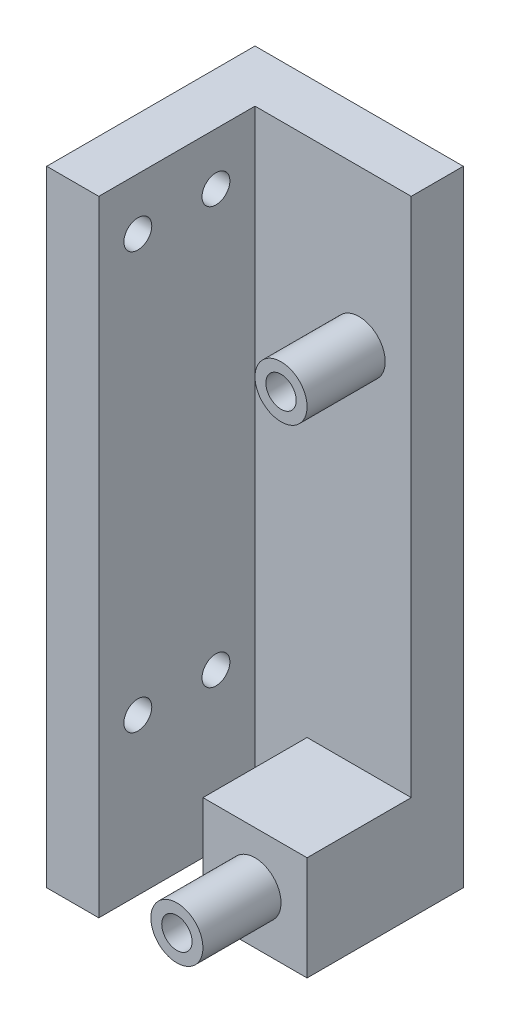
SolidWorks part; units mm, degrees
ref_plane "Front Plane" through (0, 0, 0) normal (0, 0, 1) x (1, 0, 0)
ref_plane "Top Plane" through (0, 0, 0) normal (0, 1, 0) x (1, 0, 0)
ref_plane "Right Plane" through (0, 0, 0) normal (1, 0, 0) x (0, 0, -1)
sketch "Sketch1" plane through (0, 0, 0) normal (0, 0, 1) x (1, 0, 0)
  line L1 (0, 0) -> (25.4, 0)
  line L2 (0, 0) -> (0, 76.2)
  line L3 (0, 76.2) -> (25.4, 76.2)
  line L4 (25.4, 0) -> (25.4, 76.2)
  dimension "D1" = 76.2
  dimension "D2" = 25.4
extrude "Boss-Extrude1" add sketch "Sketch1" against normal blind 25.4
sketch "Sketch10" plane through (25.4, 0, 0) normal (1, 0, 0) x (0, 0, -1)
  line L0 (25.4, 76.2) -> (0, 76.2) construction
  line L1 (19.05, 76.2) -> (0, 76.2)
  line L2 (19.05, 76.2) -> (19.05, 0)
  line L3 (19.05, 0) -> (0, 0)
  line L4 (0, 76.2) -> (0, 0)
  line L5 (25.4, 0) -> (0, 0) construction
  line L6 (25.4, 0) -> (25.4, 76.2) construction
  line L8 (0, 0) -> (0, 76.2) construction
  dimension "D1" = 6.35
extrude "Cut-Extrude5" cut sketch "Sketch10" against normal offset from surface (19.05 mm away) 6.35 up to face at (0, 38.1, -12.7)
sketch "Sketch12" plane through (0, 0, -25.4) normal (0, 0, -1) x (-1, 0, 0)
  line L0 (-25.4, 76.2) -> (0, 76.2) construction
  line L1 (-25.4, 0) -> (-25.4, 76.2) construction
  circle A1 centre (-19.05, 57.15) radius 3.175
  circle A2 centre (-19.05, 57.15) radius 1.85
  dimension "D2" = 6.35
  dimension "D4" = 3.7
  dimension "D1" = 19.05
  dimension "D3" = 6.35
extrude "Boss-Extrude2" add sketch "Sketch12" against normal blind 9.525 from surface starting at face at (15.875, 38.1, -19.05)
sketch "Sketch13" plane through (0, 0, -25.4) normal (0, 0, -1) x (-1, 0, 0)
  line L1 (-25.4, 0) -> (-12.7, 0)
  line L3 (-25.4, 12.7) -> (-12.7, 12.7)
  line L4 (-12.7, 0) -> (-12.7, 12.7)
  line L5 (-25.4, 12.7) -> (-25.4, 0)
  dimension "D2" = 12.7
  dimension "D3" = 12.7
extrude "Boss-Extrude3" add sketch "Sketch13" against normal blind 12.7 from surface starting at face at (19.05, 60.325, -19.05)
sketch "Sketch14" plane through (0, 0, -6.35) normal (0, 0, 1) x (1, 0, 0)
  line L1 (25.4, 0) -> (12.7, 0) construction
  line L2 (25.4, 12.7) -> (25.4, 76.2) construction
  circle A0 centre (19.05, 6.35) radius 1.85
  circle A1 centre (19.05, 6.35) radius 3.175
  circle A3 centre (19.05, 57.15) radius 1.85 construction
  circle A4 centre (19.05, 57.15) radius 3.175 construction
  dimension "D1" = 6.35
  dimension "D2" = 6.35
extrude "Boss-Extrude4" add sketch "Sketch14" along normal blind 9.525
sketch "Sketch15" plane through (6.35, 0, 0) normal (1, 0, 0) x (0, 0, -1)
  line L1 (19.05, 76.2) -> (0, 76.2) construction
  line L2 (0, 76.2) -> (0, 0) construction
  line L3 (19.05, 12.7) -> (19.05, 76.2) construction
  line L4 (0, 0) -> (19.05, 0) construction
  circle A0 centre (4.7625, 69.85) radius 1.7
  circle A1 centre (14.2875, 69.85) radius 1.7
  circle A2 centre (4.7625, 19.05) radius 1.7
  circle A3 centre (14.2875, 19.05) radius 1.7
  point P8 (0, 0)
  dimension "D2" = 6.35
  dimension "D1" = 3.4
  dimension "D3" = 4.7625
  dimension "D4" = 4.7625
  dimension "D5" = 19.05
extrude "Cut-Extrude6" cut sketch "Sketch15" against normal through all
equation "\"D4@Sketch12\"= 3.7mm"
equation "\"D1@Boss-Extrude1\"=(0.375+15.7mm)+0.25+0.25"
equation "\"tightTol\"= 0.005in"
equation "\"normTol\"= 0.01in"
equation "\"looseTol\"= 0.02in"
equation "\"D1@Sketch15\"=3.4mm"
